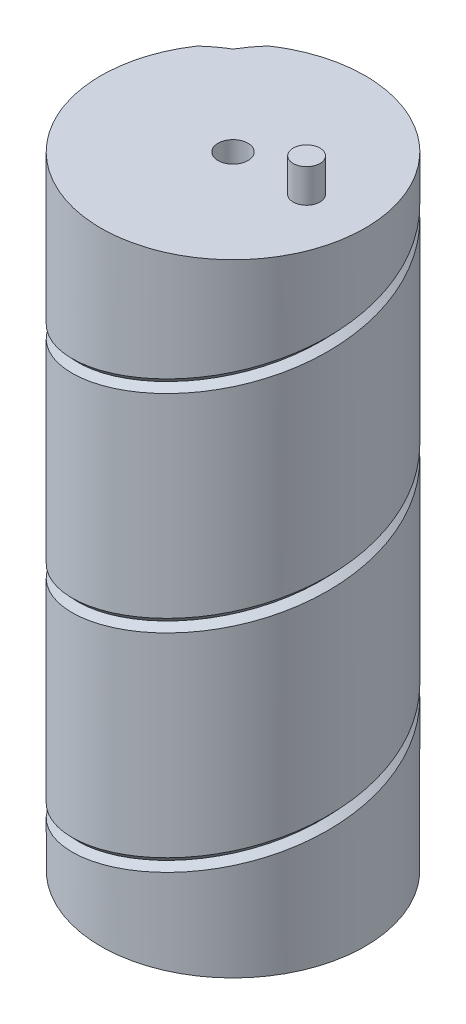
SolidWorks part; units mm, degrees
ref_plane "Front Plane" through (0, 0, 0) normal (0, 0, 1) x (1, 0, 0)
ref_plane "Top Plane" through (0, 0, 0) normal (0, 1, 0) x (1, 0, 0)
ref_plane "Right Plane" through (0, 0, 0) normal (1, 0, 0) x (0, 0, -1)
sketch "Sketch1" plane through (0, 0, 0) normal (0, 1, 0) x (1, 0, 0)
  line L0 (-19.75, 0) -> (19.75, 0) construction
  circle A0 centre (0, 0) radius 19.75
  dimension "D1" = 39.5
curve "Helix - Antenna Guide" pitch 31 height 93 radius 19.75 centre (0, 0, 0) axis (0, 1, 0) start towards (0, 0, 1)
extrude "Extrude - Main Body" add sketch "Sketch1<2>" along normal blind 93
sketch "Sketch1<2>" plane through (0, 0, 0) normal (0, 1, 0) x (1, 0, 0) same geometry as "Sketch1"
ref_point "Point2"
ref_point "Point1"
ref_plane "Plane1" through (-13.9654, 0, -13.9654) normal (-0.686, 0.2424, 0.686) x (-0.7276, -0.2285, -0.6468)
sketch "Sketch15" plane through (-13.9654, 0, -13.9654) normal (-0.686, 0.2424, 0.686) x (-0.7276, -0.2285, -0.6468)
  line L4 (0, 0) -> (0.2165, 0.8934)
  line L5 (0.2165, 0.8934) -> (-0.8934, 0.2165)
  line L8 (0, 0) -> (-0.2165, -0.8934)
  line L9 (-0.2165, -0.8934) -> (-0.8934, 0.2165)
  point P7 (-0.5549, -0.3384)
  dimension "D1" = 0.65
  dimension "D2" = 90
sweep "Cut - Antenna Wire Guide" cut profiles "Sketch15" path "Helix - Antenna Guide" align with end faces yes
sketch "Sketch23" plane through (0, 0, 0) normal (0, -1, 0) x (1, 0, 0)
  line L0 (-13.3154, -13.3154) -> (-8.3849, -14.1466)
  line L1 (-9.335, -17.4046) -> (-10.0329, -12.4535)
  arc A0 (-11.0473, -16.3713) -> (-16.3713, -11.0473) centre (0, 0) ccw construction
  arc A1 (-10.0329, -12.4535) -> (-8.3849, -14.1466) centre (-8.0525, -12.1744) cw
  arc A2 (-9.335, -17.4046) -> (-13.3154, -13.3154) centre (-14.1184, -18.0788) cw
  dimension "D2" = 2
  dimension "D1" = 2
  dimension "D3" = 5
  dimension "D4" = 5
ref_plane "Plane - Anchor Loop Exit" through (-9.335, 0, -17.4046) normal (-0.1396, 0, 0.9902) x (0.9902, 0, 0.1396)
ref_plane "Plane - Anchor Loop Peg" through (-10.0329, 0, -12.4535) normal (-0.1396, 0, 0.9902) x (0.9902, 0, 0.1396)
sketch "Sketch28" plane through (0, 93, 0) normal (0, 1, 0) x (1, 0, 0)
  circle A0 centre (11, 0) radius 2
  point P0 (0, 0)
  point P4 (0, 0)
  dimension "D1" = 4
  dimension "D2" = 11
extrude "Boss-Extrude3" add sketch "Sketch28" along normal blind 5
hole_wizard "#8 Clearance Hole1" positions "Sketch29" profile "Sketch30" hole size "#8" standard "ANSI Inch" end condition through all
sketch "Sketch29" plane through (0, 93, 0) normal (0, 1, 0) x (1, 0, 0)
  point P0 (0, 0)
sketch "Sketch30" plane through (0, 93, 0) normal (1, 0, 0) x (0, 0, 1)
  line L0 (0, 0) -> (0, 94.4693)
  line L1 (0, 94.4693) -> (2.2479, 94.4693)
  line L2 (2.2479, 94.4693) -> (2.2479, 0)
  line L5 (2.2479, 0) -> (0, 0)
  line L11 (0, -6.35) -> (0, 107.95) construction
  dimension "Thru Hole Dia." = 4.4958
  dimension "Thru Hole Depth" = 94.4693
sketch "Sketch31" plane through (0, 0, 0) normal (0, -1, 0) x (1, 0, 0)
  circle A0 centre (11, 0) radius 2.25
  dimension "D1" = 4.5
  dimension "D2" = 11
extrude "Cut-Extrude1" cut sketch "Sketch31" against normal blind 5.5
equation "\"pegD\"=10"
equation "\"pegHoleD\"=0.5"
equation "\"pegHoleOffset\"=0.5"
